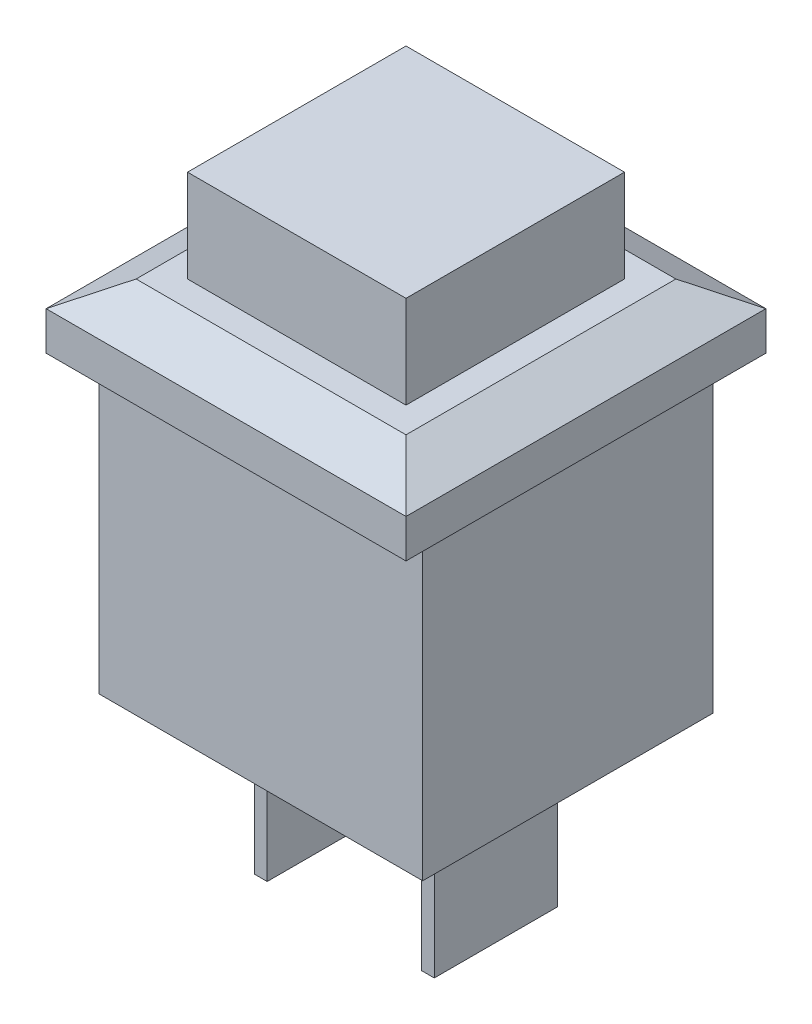
SolidWorks part; units mm, degrees
ref_plane "Front Plane" through (0, 0, 0) normal (0, 0, 1) x (1, 0, 0)
ref_plane "Top Plane" through (0, 0, 0) normal (0, 1, 0) x (1, 0, 0)
ref_plane "Right Plane" through (0, 0, 0) normal (1, 0, 0) x (0, 0, -1)
sketch "Bezel drawing" plane through (0, 0, 0) normal (0, 1, 0) x (1, 0, 0)
  line L1 (-7, -7) -> (7, -7)
  line L2 (-7, -7) -> (-7, 7)
  line L3 (-7, 7) -> (7, 7)
  line L4 (7, -7) -> (7, 7)
  line L5 (-7, -7) -> (7, 7) construction
  line L6 (-7, 7) -> (7, -7) construction
  point P0 (0, 0)
  dimension "D1" = 14
  dimension "D2" = 14
extrude "Bezel" add sketch "Bezel drawing" along normal blind 2.5
chamfer "Chamfer1" distance 1 distance2 1.75 4 edges at (0, 2.5, 7) (-7, 2.5, 0) (0, 2.5, -7) (7, 2.5, 0) first distance on face at (0, 1.25, 7) first distance on face at (-7, 1.25, 0) first distance on face at (0, 1.25, -7) first distance on face at (7, 1.25, 0)
sketch "Sketch2" plane through (0, 2.5, 0) normal (0, 1, 0) x (1, 0, 0)
  line L1 (-4.25, 4.25) -> (4.25, 4.25)
  line L2 (-4.25, 4.25) -> (-4.25, -4.25)
  line L3 (-4.25, -4.25) -> (4.25, -4.25)
  line L4 (4.25, 4.25) -> (4.25, -4.25)
  line L5 (-4.25, 4.25) -> (4.25, -4.25) construction
  line L6 (-4.25, -4.25) -> (4.25, 4.25) construction
  point P0 (0, 0)
  dimension "D1" = 8.5
  dimension "D2" = 8.5
extrude "Boss-Extrude2" add sketch "Sketch2" along normal blind 3.6 separate body
sketch "Sketch3" plane through (0, 0, 0) normal (0, -1, 0) x (1, 0, 0)
  line L1 (6.3, -5.65) -> (-6.3, -5.65)
  line L2 (6.3, -5.65) -> (6.3, 5.65)
  line L3 (6.3, 5.65) -> (-6.3, 5.65)
  line L4 (-6.3, -5.65) -> (-6.3, 5.65)
  line L5 (6.3, -5.65) -> (-6.3, 5.65) construction
  line L6 (6.3, 5.65) -> (-6.3, -5.65) construction
  point P0 (0, 0)
  dimension "D1" = 12.6
  dimension "D2" = 11.3
extrude "Boss-Extrude3" add sketch "Sketch3" along normal blind 11.8
sketch "Sketch4" plane through (0, -11.8, 0) normal (0, -1, 0) x (1, 0, 0)
  line L0 (0, 0) -> (-8.7597, 0) construction
  line L1 (-3.5, -2.4) -> (-3, -2.4)
  line L2 (-3.5, -2.4) -> (-3.5, 2.4)
  line L3 (-3.5, 2.4) -> (-3, 2.4)
  line L4 (-3, -2.4) -> (-3, 2.4)
  line L5 (-3.5, -2.4) -> (-3, 2.4) construction
  line L6 (-3.5, 2.4) -> (-3, -2.4) construction
  line L7 (0, 0) -> (0, 4.4901) construction
  line L8 (3, -2.4) -> (3, 2.4)
  line L9 (3.5, -2.4) -> (3, -2.4)
  line L10 (3.5, -2.4) -> (3.5, 2.4)
  line L11 (3.5, 2.4) -> (3, 2.4)
  point P0 (-3.25, 0)
  dimension "D1" = 0.5
  dimension "D2" = 4.8
  dimension "D3" = 3.25
extrude "Boss-Extrude4" add sketch "Sketch4" along normal blind 6.3
ref_axis "Vertical Centerline" through (0, 0, 0) along (0, 0, -1)
ref_axis "Horizontal Centerline" through (0, 0, 0) along (-1, 0, 0)
ref_plane "Midplane" through (0, 0, 0) normal (-1, 0, 0) x (0, 0, 1)
ref_plane "Plane1" through (0, 0, 0) normal (0, 0, -1) x (-1, 0, 0)
ref_axis "Centerline" through (0, -21.0509, 0) along (0, 1, 0)
